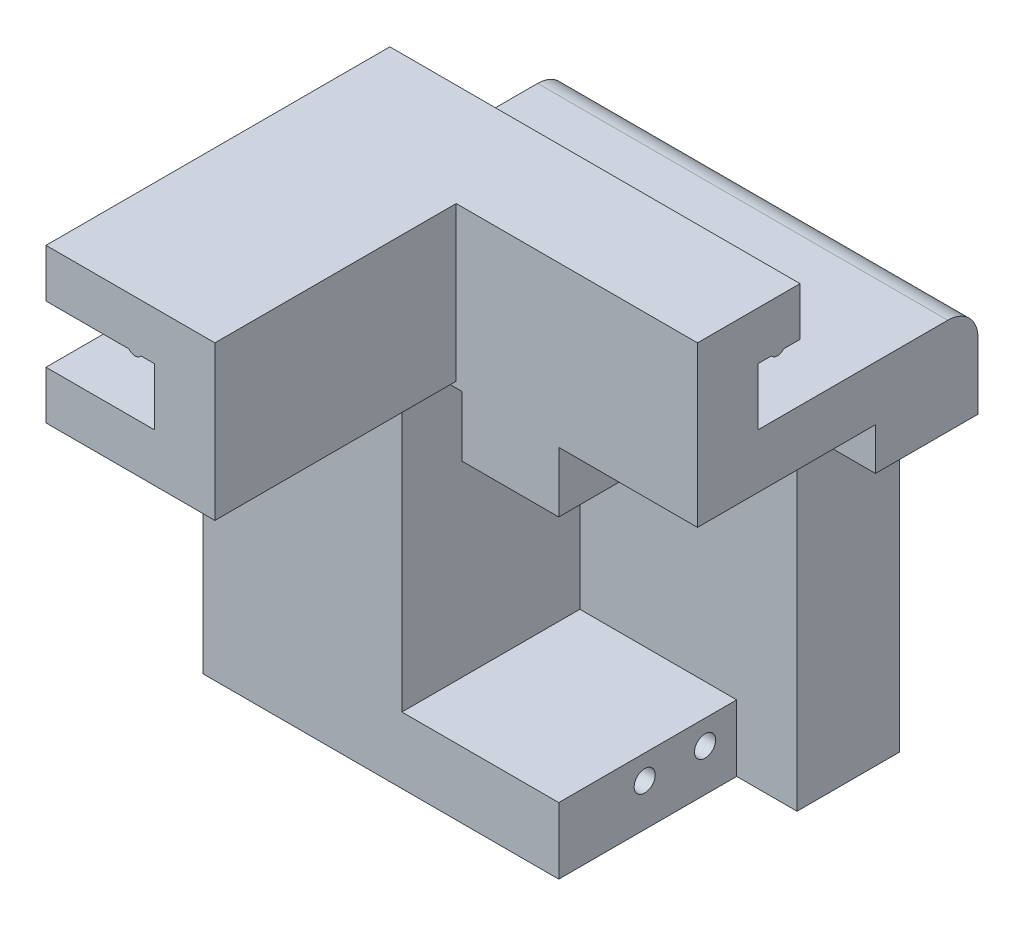
SolidWorks part; units mm, degrees
ref_plane "Front Plane" through (0, 0, 0) normal (0, 0, 1) x (1, 0, 0)
ref_plane "Top Plane" through (0, 0, 0) normal (0, 1, 0) x (1, 0, 0)
ref_plane "Right Plane" through (0, 0, 0) normal (1, 0, 0) x (0, 0, -1)
sketch "Sketch1" plane through (0, 0, 0) normal (0, 0, 1) x (1, 0, 0)
  line L0 (0, 0) -> (-18, 0)
  line L1 (-18, 0) -> (-18, -8)
  line L2 (-18, -8) -> (0, -8)
  line L3 (0, -8) -> (0, -17.5)
  line L4 (0, -17.5) -> (-18, -17.5)
  line L5 (-18, -17.5) -> (-18, -25.5)
  line L6 (-18, -25.5) -> (10, -25.5)
  line L7 (10, -25.5) -> (10, 0)
  line L8 (10, 0) -> (0, 0)
  arc A0 (-4.25, -8) -> (-2.25, -8) centre (-3.25, -7.25) ccw
  point P13 (-3.25, -8.5)
  dimension "D7" = 3.25
  dimension "D1" = 18
  dimension "D2" = 9.5
  dimension "D3" = 8
  dimension "D4" = 8
  dimension "D5" = 10
  dimension "D6" = 9
  dimension "D8" = 1
  dimension "D9" = 28
extrude "Boss-Extrude1" add sketch "Sketch1" along normal blind 50 contours L2 A0 | L7 L8 L0 L1 L2 L3 L4 L5 L6 region at (5, -0.3787, 0) region at (-3.25, -8.2039, 0)
sketch "Sketch2" plane through (0, 0, 0) normal (1, 0, 0) x (0, 0, -1)
  line L9 (0, 0) -> (0, -50) construction
  line L10 (7, -8) -> (0, -8)
  line L11 (0, -17.5) -> (7, -17.5)
  line L12 (0, -8) -> (0, -17.5)
  line L13 (7, -17.5) -> (7, -25.5)
  line L14 (7, -25.5) -> (-10, -25.5)
  line L15 (-10, -25.5) -> (-10, 0)
  line L16 (-10, 0) -> (0, 0)
  line L17 (0, 0) -> (7, 0)
  line L18 (7, 0) -> (7, -8)
  arc A1 (4.25, -8) -> (2.25, -8) centre (3.25, -7.25) cw
  dimension "D13" = 1.25
  dimension "D2" = 17
  dimension "D3" = 3.25
  dimension "D4" = 25.5
  dimension "D5" = 1
  dimension "D6" = 9.5
  dimension "D7" = 8
  dimension "D8" = 8
  dimension "D9" = 10
  dimension "D10" = 10
  dimension "D11" = 50
  dimension "D12" = 7
  dimension "D16" = 0.75
extrude "Boss-Extrude2" add sketch "Sketch2" along normal blind 50 contours L17 L9 L10 L18 | L9 L16 L15 L14 L12 | L11 L9 L14 L13 | A1 L10 region at (0, -4, -3.5) region at (0, -12.75, 5) region at (0, -21.5, -3.5) region at (0, -8.2039, -3.25)
extrude "Boss-Extrude3" add sketch "Sketch2<3>" against normal up to surface (18 mm away) contours L17 L9 L10 L18 | L11 L9 L14 L13 region at (0, -4, -3.5) region at (0, -21.5, -3.5) up to face at (-18, -4, 25)
sketch "Sketch2<3>" plane through (0, 0, 0) normal (1, 0, 0) x (0, 0, -1) same geometry as "Sketch2"
sketch "Sketch3" plane through (50, 0, 0) normal (1, 0, 0) x (0, 0, -1)
  line L0 (0, -17.5) -> (36.5, -17.5)
  line L1 (0, -25.5) -> (0, -88.5)
  line L2 (7, -25.5) -> (-10, -25.5) construction
  line L3 (0, -17.5) -> (0, -25.5)
  line L4 (36.5, -17.5) -> (36.5, -88.5)
  line L5 (36.5, -88.5) -> (0, -88.5)
  line L6 (0, -17.5) -> (-10, -17.5)
  line L7 (-10, -25.5) -> (-10, 0) construction
  line L8 (-10, -17.5) -> (-10, -88.5)
  line L9 (-10, -88.5) -> (0, -88.5)
  line M3 (-10, 0) -> (-10, -25.5)
  line M4 (-10, -25.5) -> (7, -25.5)
  line M5 (7, -25.5) -> (7, -17.5)
  line M6 (7, -17.5) -> (0, -17.5)
  dimension "D1" = 36.5
  dimension "D2" = 63
ref_plane "Wall" through (-32, 0, 0) normal (-1, 0, 0) x (0, 0, 1)
extrude "Boss-Extrude4" add sketch "Sketch3" against normal up to surface (82 mm away) contours L5 L4 L0 L1 M5 M4 | L8 L9 L1 M4 | L3 M6 M4 M5 | L3 L6 M3 M4 region at (50, -21.5, -3.5) region at (50, -21.5, 5) region at (50, -53.6957, -18.5758) region at (50, -57, 5) up to plane "Wall"
fillet "Fillet1" radius 5 3 edges at (-32, -53, -36.5) (-32, -17.5, -13.25) (9, -17.5, -36.5)
sketch "Sketch4" plane through (0, -88.5, 0) normal (0, -1, 0) x (1, 0, 0)
  line L0 (50, 10) -> (50, -19.5)
  line L1 (50, -36.5) -> (50, 10) construction
  line L2 (50, -19.5) -> (1, -19.5)
  line L3 (1, -19.5) -> (1, 10)
  line L4 (-18, 10) -> (10, 10) construction
  line L5 (1, 10) -> (50, 10)
  line L6 (-32, -31.5) -> (-32, 10) construction
  line L7 (-27, -36.5) -> (50, -36.5) construction
  dimension "D1" = 33
  dimension "D2" = 17
extrude "Cut-Extrude1" cut sketch "Sketch4" against normal up to surface (63 mm away) up to face at (-4, -25.5, 30)
sketch "Sketch5" plane through (50, 0, 0) normal (1, 0, 0) x (0, 0, -1)
  line L0 (-10, -36.5) -> (19.5, -36.5)
  line L1 (-10, -25.5) -> (-10, -88.5) construction
  line L2 (19.5, -25.5) -> (19.5, -88.5) construction
  line L3 (19.5, -36.5) -> (19.5, -77.5)
  line L4 (19.5, -77.5) -> (-10, -77.5)
  line L5 (-10, -77.5) -> (-10, -36.5)
  line L6 (0, -17.5) -> (31.5, -17.5) construction
  line L7 (-10, -36.5) -> (-10, -25.5)
  line L8 (-10, -25.5) -> (19.5, -25.5)
  line L9 (19.5, -25.5) -> (19.5, -36.5)
  line L10 (-10, -77.5) -> (-10, -88.5)
  line L11 (-10, -88.5) -> (19.5, -88.5)
  line L12 (19.5, -88.5) -> (19.5, -77.5)
  line M3 (-10, -25.5) -> (19.5, -25.5)
  line M4 (19.5, -25.5) -> (19.5, -88.5)
  dimension "D1" = 19
  dimension "D2" = 41
extrude "Boss-Extrude5" add sketch "Sketch5" against normal up to surface (49 mm away) contours L7 L0 M4 M3 | L10 L11 L4 M4 region at (50, -31, -4.75) region at (50, -83, -4.75) up to face at (1, -57, -4.75)
sketch "Sketch7" plane through (0, 0, 10) normal (0, 0, 1) x (1, 0, 0)
  line L0 (1, -36.5) -> (27, -36.5)
  line L1 (1, -36.5) -> (50, -36.5) construction
  line L2 (27, -36.5) -> (27, -26.5)
  line L3 (27, -26.5) -> (50, -26.5)
  line L4 (50, -36.5) -> (50, 0) construction
  line L5 (50, -26.5) -> (50, -88.5)
  line L6 (50, -88.5) -> (27, -88.5)
  line L7 (-32, -88.5) -> (50, -88.5) construction
  line L8 (27, -88.5) -> (27, -77.5)
  line L9 (1, -77.5) -> (50, -77.5) construction
  line L10 (27, -77.5) -> (1, -77.5)
  line L11 (1, -77.5) -> (1, -36.5)
  dimension "D1" = 26
  dimension "D2" = 26
  dimension "D3" = 10
extrude "Cut-Extrude2" cut sketch "Sketch7" against normal up to surface (29.5 mm away) up to face at (25.5, -57, -19.5)
sketch "Sketch6" plane through (27, 0, 0) normal (1, 0, 0) x (0, 0, -1)
  line L0 (-10, -36.5) -> (-10, -77.5) construction
  line L1 (36.5, -57) -> (-10, -57)
  line L2 (-1, -57) -> (19.5, -57)
  line L4 (9.25, -57) -> (9.25, -88.5)
  line L5 (36.5, -88.5) -> (19.5, -88.5) construction
  line L6 (4.25, -81.5) -> (14.25, -81.5)
  line L7 (36.5, -22.5) -> (36.5, -88.5) construction
  line L8 (0, -17.5) -> (31.5, -17.5) construction
  line L9 (19.5, -26.5) -> (19.5, -88.5) construction
  circle A0 centre (4.25, -81.5) radius 1.75
  circle A1 centre (14.25, -81.5) radius 1.75
  circle A2 centre (4.25, -81.5) radius 0.75
  circle A3 centre (14.25, -81.5) radius 0.75
  circle A4 centre (14.25, -32.5) radius 0.75
  circle A5 centre (14.25, -32.5) radius 1.75
  circle A6 centre (4.25, -32.5) radius 0.75
  circle A7 centre (4.25, -32.5) radius 1.75
  point P16 (9.25, -81.5)
  dimension "D4" = 3.5
  dimension "D5" = 1.5
  dimension "D6" = 1.5
  dimension "D7" = 3.5
  dimension "D1" = 24.5
  dimension "D2" = 24.5
  dimension "D3" = 10
  dimension "D8" = 20.5
  dimension "D9" = 39.5
  dimension "D10" = 0
extrude "Cut-Extrude3" cut sketch "Sketch6" against normal blind 5 contours A7 A6 | A6 | A5 A4 | A4 | A2 A0 | A2 | A3 A1 | A3 region at (27, -81.5, -2.5495) region at (27, -80.7712, -14.25) region at (27, -79.7995, -14.25) region at (27, -81.5, -3.5212) region at (27, -32.5, -14.25) region at (27, -32.5, -12.5495) region at (27, -32.5, -4.25) region at (27, -32.5, -2.5495)
extrude "Cut-Extrude4" cut sketch "Sketch6<6>" against normal blind 15 contours A6 | A4 | A2 | A3 region at (27, -81.5, -3.5212) region at (27, -32.5, -14.25) region at (27, -32.5, -4.25)
sketch "Sketch6<6>" plane through (27, 0, 0) normal (1, 0, 0) x (0, 0, -1) same geometry as "Sketch6"
sketch "Sketch8" plane through (0, 0, -7) normal (0, 0, -1) x (-1, 0, 0)
  line L0 (0, -8) -> (18, -8)
  line L1 (18, -8) -> (18, -17.5)
  line L2 (-50, -17.5) -> (27, -17.5) construction
  line L3 (18, -17.5) -> (0, -17.5)
  line L4 (0, -17.5) -> (0, -8)
extrude "Cut-Extrude5" cut sketch "Sketch8" against normal blind 40
sketch "Sketch9" plane through (-18, 0, 0) normal (-1, 0, 0) x (0, 0, 1)
  line L0 (-7, -8) -> (0, -8)
  line L1 (0, -8) -> (0, -17.5)
  line L2 (0, -17.5) -> (-7, -17.5)
  line L3 (-31.5, -17.5) -> (10, -17.5) construction
  line L4 (-7, -17.5) -> (-7, -8)
extrude "Cut-Extrude6" cut sketch "Sketch9" against normal blind 45
sketch "Sketch10" plane through (0, 0, 10) normal (0, 0, 1) x (1, 0, 0)
  line L0 (1, -36.5) -> (11, -36.5)
  line L1 (1, -36.5) -> (27, -36.5) construction
  line L2 (11, -36.5) -> (11, -26.5)
  line L3 (11, -26.5) -> (1, -26.5)
  line L4 (1, -26.5) -> (1, -36.5)
  dimension "D1" = 10
  dimension "D2" = 10
extrude "Cut-Extrude7" cut sketch "Sketch10" against normal up to surface (29.5 mm away) up to face at (26.25, -57.25, -19.5)
sketch "Sketch11" plane through (0, 0, -19.5) normal (0, 0, 1) x (1, 0, 0)
  line L1 (27, -88.5) -> (50, -88.5) construction
  line L2 (37, -88.5) -> (50, -88.5)
  line L3 (50, -88.5) -> (50, -26.5)
  line L4 (50, -26.5) -> (37, -26.5)
  line L5 (50, -26.5) -> (27, -26.5) construction
  line L8 (37, -26.5) -> (37, -88.5)
  line L9 (27, -26.5) -> (27, -36.5) construction
  line L10 (37, -33.5) -> (50, -33.5)
  line L11 (37, -81.5) -> (50, -81.5)
  line M5 (27, -88.5) -> (50, -88.5)
  line M6 (50, -88.5) -> (50, -26.5)
  dimension "D1" = 10
  dimension "D2" = 7
  dimension "D3" = 7
extrude "Cut-Extrude8" cut sketch "Sketch11" against normal through all contours L8 L11 L3 L10 | L11 L8 M5 M6 region at (43.5, -85, -19.5) region at (43.5, -57.5, -19.5)
sketch "Sketch12" plane through (0, -88.5, 0) normal (0, -1, 0) x (1, 0, 0)
  line L0 (-32, -26.5) -> (-24, -26.5)
  line L1 (-32, -31.5) -> (-32, 10) construction
  line L2 (-24, -26.5) -> (-24, -36.5)
  line L3 (-27, -36.5) -> (37, -36.5) construction
  line L4 (-32, -26.5) -> (-32, -36.5)
  line L5 (-32, -36.5) -> (-24, -36.5)
  dimension "D1" = 8
  dimension "D2" = 10
extrude "Cut-Extrude9" cut sketch "Sketch12" against normal through all
sketch "Sketch13" plane through (-32, 0, 0) normal (-1, 0, 0) x (0, 0, 1)
  line L4 (-26.5, -17.5) -> (-36.5, -17.5)
  line L5 (-36.5, -17.5) -> (-36.5, -23.5)
  line L6 (-36.5, -23.5) -> (-26.5, -23.5)
  line L7 (-26.5, -17.5) -> (-26.5, -88.5) construction
  line L8 (-26.5, -23.5) -> (-26.5, -17.5)
  dimension "D1" = 6
  dimension "D2" = 10
extrude "Cut-Extrude10" cut sketch "Sketch13" against normal up to surface (14 mm away) up to face at (-18, -21.5, 30)
sketch "Sketch14" plane through (0, 0, 10) normal (0, 0, 1) x (1, 0, 0)
  line L10 (10, -17.5) -> (16, -17.5)
  line L11 (10, -25.5) -> (10, 0) construction
  line L12 (16, -17.5) -> (16, -23.5)
  line L13 (16, -23.5) -> (10, -23.5)
  line L14 (10, -23.5) -> (10, -17.5)
  dimension "D1" = 6
  dimension "D2" = 6
sketch "Sketch15" plane through (0, 0, -26.5) normal (0, 0, -1) x (-1, 0, 0)
  line L0 (18, -23.5) -> (18, -17.5)
  line L1 (18, -17.5) -> (32, -17.5)
  line L2 (32, -5.225) -> (32, 5.225) construction
  line L3 (32, -17.5) -> (32, -23.5)
  line L4 (32, -22.5) -> (32, -88.5) construction
  line L5 (32, -23.5) -> (18, -23.5)
extrude "Cut-Extrude11" cut sketch "Sketch15" against normal through all
fillet "Fillet2" radius 3 3 edges at (-28, -23.5, -26.5) (-24, -56, -26.5) (-24, -23.5, -31.5)
